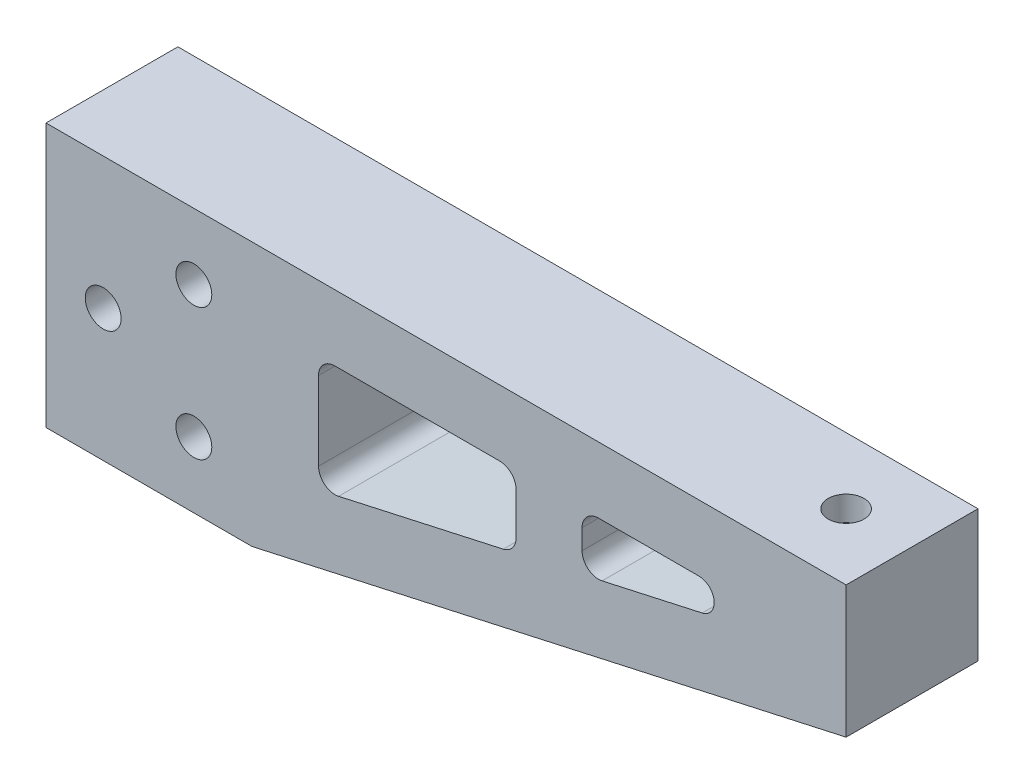
SolidWorks part; units mm, degrees
material "Onyx w/ CF"
ref_plane "Front Plane" through (0, 0, 0) normal (0, 0, 1) x (1, 0, 0)
ref_plane "Top Plane" through (0, 0, 0) normal (0, 1, 0) x (1, 0, 0)
ref_plane "Right Plane" through (0, 0, 0) normal (1, 0, 0) x (0, 0, -1)
sketch "Sketch1" plane through (0, 0, 0) normal (0, 0, 1) x (1, 0, 0)
  line L1 (0, 12.7) -> (-77.0433, 12.7)
  line L2 (0, 12.7) -> (0, -12.7)
  line L3 (0, -12.7) -> (-77.0433, -12.7)
  line L4 (-77.0433, 12.7) -> (-77.0433, -12.7)
  point P5 (0, 0)
  dimension "D1" = 25.4
  dimension "D2" = 77.0433
extrude "Boss-Extrude1" add sketch "Sketch1" along normal mid plane 12.7
sketch "Sketch2" plane through (0, 12.7, 0) normal (0, 1, 0) x (1, 0, 0)
  line L1 (-3.4013, -2.9487) -> (-9.2988, -2.9487)
  line L2 (-3.4013, -2.9487) -> (-3.4013, 2.9488)
  line L3 (-3.4013, 2.9488) -> (-9.2988, 2.9488)
  line L4 (-9.2988, -2.9487) -> (-9.2988, 2.9488)
  line L5 (-3.4013, -2.9487) -> (-9.2988, 2.9488) construction
  line L6 (-3.4013, 2.9488) -> (-9.2988, -2.9487) construction
  point P0 (-6.35, 0)
  dimension "D1" = 5.8975
extrude "Cut-Extrude1" cut sketch "Sketch2" against normal blind 2.1764 from offset 2.3812 offset against normal yes
hole_wizard "#4 Clearance Hole1" positions "Sketch3" profile "Sketch4" hole size "#4" standard "ANSI Inch"
sketch "Sketch3" plane through (0, 12.7, 0) normal (0, 1, 0) x (1, 0, 0)
  point P0 (-6.35, 0)
sketch "Sketch4" plane through (-6.35, 12.7, 0) normal (1, 0, 0) x (0, 0, 1)
  line L0 (0, 0) -> (0, 7.3878)
  line L1 (0, 7.3878) -> (1.7272, 6.35)
  line L2 (1.7272, 6.35) -> (1.7272, 0)
  line L5 (1.7272, 0) -> (0, 0)
  line L10 (0, 7.3878) -> (-1.7272, 6.35) construction
  line L11 (0, -6.35) -> (0, 107.95) construction
  dimension "Hole Dia." = 3.4544
  dimension "Hole Depth" = 6.35
  dimension "Drill Angle" = 118
hole_wizard "#4 Clearance Hole2" positions "Sketch5" profile "Sketch7" hole size "#4" standard "ANSI Inch" end condition through all
sketch "Sketch5" plane through (0, 0, 6.35) normal (0, 0, 1) x (1, 0, 0)
  point P0 (-62.8066, -6.35)
  point P3 (-71.5378, 0)
  point P6 (-62.8066, 6.35)
sketch "Sketch7" plane through (-62.8066, -6.35, 6.35) normal (1, 0, 0) x (0, -1, 0)
  line L0 (0, 0) -> (0, 12.7)
  line L1 (0, 12.7) -> (1.7272, 12.7)
  line L2 (1.7272, 12.7) -> (1.7272, 0)
  line L5 (1.7272, 0) -> (0, 0)
  line L11 (0, -6.35) -> (0, 107.95) construction
  dimension "Thru Hole Dia." = 3.4544
  dimension "Thru Hole Depth" = 12.7
sketch "Sketch8" plane through (0, 0, -6.35) normal (0, 0, -1) x (-1, 0, 0)
  line L0 (0, 0) -> (0, -12.7)
  line L1 (0, -12.7) -> (0, 12.7) construction
  line L2 (0, -12.7) -> (57.1995, -12.7)
  line L3 (77.0433, -12.7) -> (0, -12.7) construction
  line L4 (57.1995, -12.7) -> (0, 0)
  dimension "D1" = 19.8438
  dimension "D2" = 12.7
extrude "Cut-Extrude2" cut sketch "Sketch8" against normal through all
sketch "Sketch9" plane through (0, 0, 6.35) normal (0, 0, 1) x (1, 0, 0)
  line L0 (-12.7, 3.6849) -> (-25.4248, 0.8596)
  line L1 (-25.4248, 0.8596) -> (-25.4248, 6.35)
  line L2 (-25.4248, 6.35) -> (-12.7, 6.35)
  line L3 (-12.7, 6.35) -> (-12.7, 3.6849)
  line L4 (-31.7748, -0.5503) -> (-50.8016, -4.7748)
  line L5 (-50.8016, -4.7748) -> (-50.8016, 6.35)
  line L6 (-50.8016, 6.35) -> (-31.7748, 6.35)
  line L7 (-31.7748, 6.35) -> (-31.7748, -0.5503)
  line L8 (0, 0) -> (0, 12.7) construction
  line L9 (-57.1516, 12.7) -> (-57.1516, -12.7) construction
  line L10 (-57.1995, -12.7) -> (0, 0) construction
  line L11 (0, 12.7) -> (-77.0433, 12.7) construction
  line L12 (0, 12.7) -> (-57.1995, 12.7) construction
  line L13 (-25.4248, 6.35) -> (-31.7748, 6.35) construction
  point P16 (-28.5998, 6.35)
  point P20 (-28.5998, 12.7)
  dimension "D1" = 12.7
  dimension "D2" = 6.35
  dimension "D3" = 6.35
  dimension "D4" = 6.35
  dimension "D5" = 6.35
  dimension "D6" = 19.8438
extrude "Cut-Extrude3" cut sketch "Sketch9" against normal through all
fillet "Fillet1" radius 1.5875 6 edges at (-50.8016, -4.7748, 0) (-50.8016, 6.35, 0) (-31.7748, 6.35, 0) (-31.7748, -0.5503, 0) (-25.4248, 6.35, 0) (-25.4248, 0.8596, 0)
fillet "Fillet2" 2 edges at (-12.7, 6.35, 0) (-12.7, 3.6849, 0) type full round first side face at (-18.2686, 6.35, 0) second side face at (-18.0966, 2.4867, 0) middle face at (-12.7, 5.0174, 0)
